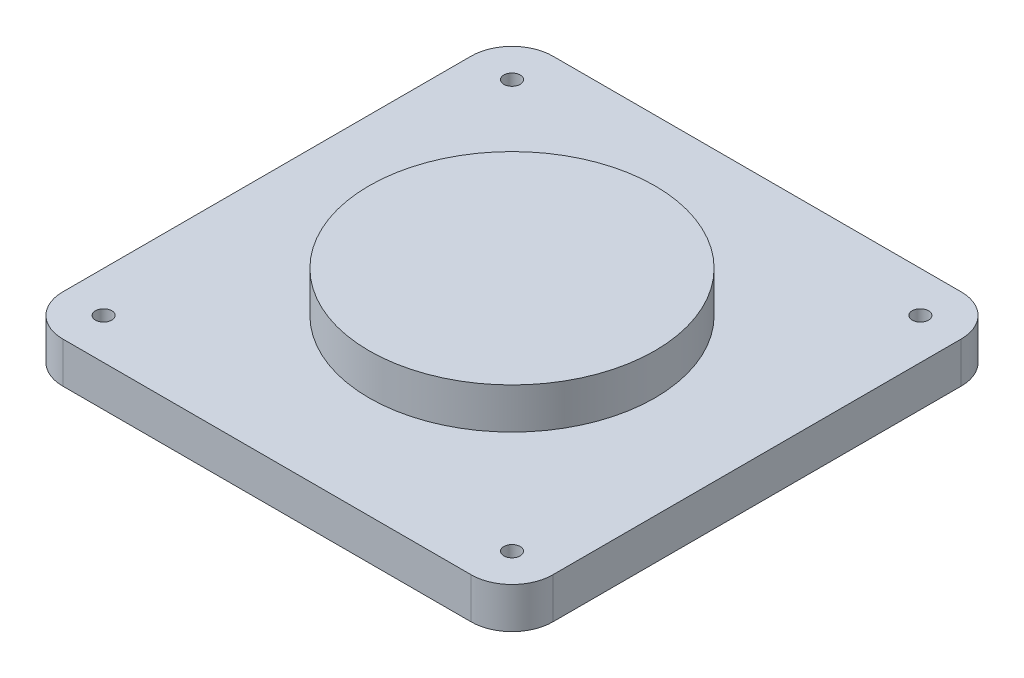
SolidWorks part; units mm, degrees
ref_plane "前视基准面" through (0, 0, 0) normal (0, 0, 1) x (1, 0, 0)
ref_plane "上视基准面" through (0, 0, 0) normal (0, 1, 0) x (1, 0, 0)
ref_plane "右视基准面" through (0, 0, 0) normal (1, 0, 0) x (0, 0, -1)
sketch "草图1" plane through (0, 0, 0) normal (0, 1, 0) x (1, 0, 0)
  line L1 (-50, 60) -> (50, 60)
  line L2 (-60, 50) -> (-60, -50)
  line L3 (-50, -60) -> (50, -60)
  line L4 (60, 50) -> (60, -50)
  line L5 (-60, 60) -> (60, -60) construction
  line L6 (-60, -60) -> (60, 60) construction
  line L7 (-50, 50) -> (50, 50) construction
  line L8 (-50, 50) -> (-50, -50) construction
  line L9 (-50, -50) -> (50, -50) construction
  line L10 (50, 50) -> (50, -50) construction
  line L11 (-50, 50) -> (50, -50) construction
  line L12 (-50, -50) -> (50, 50) construction
  circle A0 centre (-50, 50) radius 2
  circle A1 centre (-50, -50) radius 2
  circle A2 centre (50, 50) radius 2
  circle A3 centre (50, -50) radius 2
  arc A4 (50, -60) -> (60, -50) centre (50, -50) ccw
  arc A5 (50, 60) -> (60, 50) centre (50, 50) cw
  arc A6 (-60, -50) -> (-50, -60) centre (-50, -50) ccw
  arc A7 (-50, 60) -> (-60, 50) centre (-50, 50) ccw
  point P0 (0, 0)
  point P6 (0, 0)
  dimension "D3" = 4
  dimension "D4" = 10
  dimension "D1" = 120
  dimension "D2" = 100
extrude "凸台-拉伸1" add sketch "草图1" along normal blind 10
sketch "草图2" plane through (0, 10, 0) normal (0, 1, 0) x (1, 0, 0)
  circle A0 centre (0, 0) radius 35
  dimension "D1" = 70
extrude "凸台-拉伸2" add sketch "草图2" along normal blind 10
